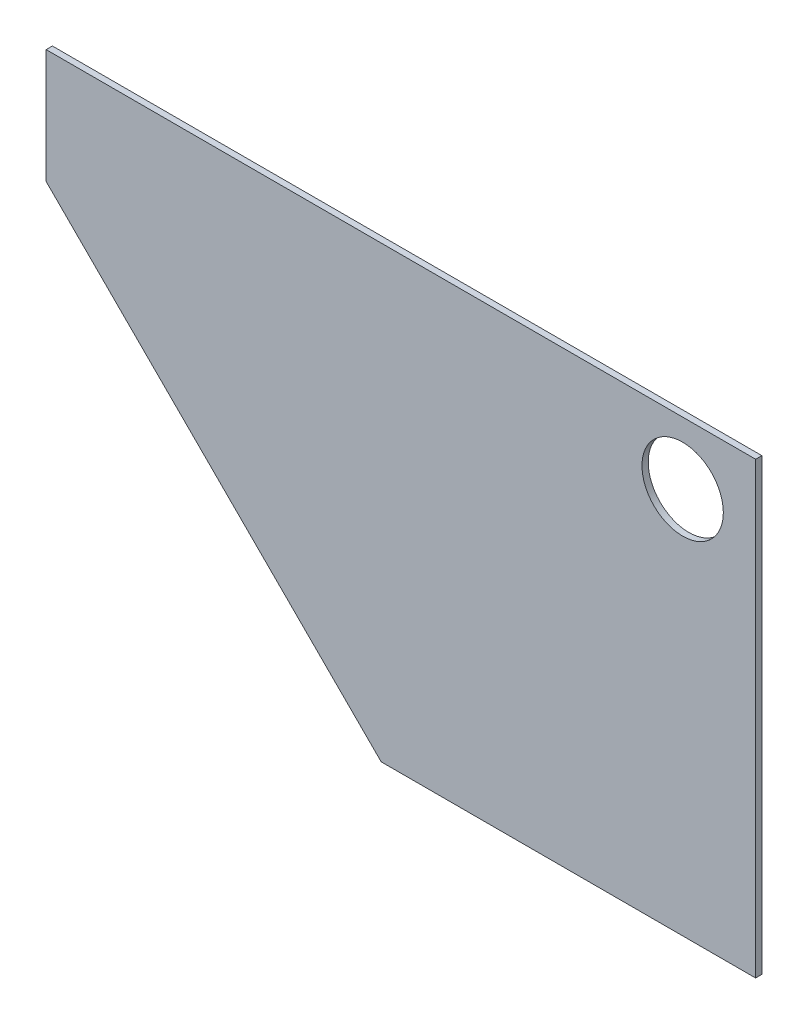
SolidWorks part; units mm, degrees
ref_plane "Front Plane" through (0, 0, 0) normal (0, 0, 1) x (1, 0, 0)
ref_plane "Top Plane" through (0, 0, 0) normal (0, 1, 0) x (1, 0, 0)
ref_plane "Right Plane" through (0, 0, 0) normal (1, 0, 0) x (0, 0, -1)
sketch "Sketch1" plane through (0, 0, 0) normal (0, 0, 1) x (1, 0, 0)
  line L0 (-138.2594, 48.9915) -> (32.2106, -121.4785)
  line L1 (32.2106, -121.4785) -> (222.7106, -121.4785)
  line L2 (-138.2594, 107.1215) -> (-138.2594, 48.9915)
  line L3 (-138.2594, 107.1215) -> (222.7106, 107.1215)
  line L4 (222.7106, -121.4785) -> (222.7106, 107.1215)
  circle A0 centre (185.5906, 75.3715) radius 20.701
  circle A2 centre (185.5906, 75.3715) radius 69.85 construction
  circle A3 centre (185.5906, 75.3715) radius 323.85 construction
  point P0 (0, 0)
  point P2 (185.5906, 75.3715)
  dimension "D4" = 196.85
  dimension "D1" = 45
  dimension "D2" = 228.6
  dimension "D5" = 247.65
extrude "Boss-Extrude1" add sketch "Sketch1" along normal blind 3.175
